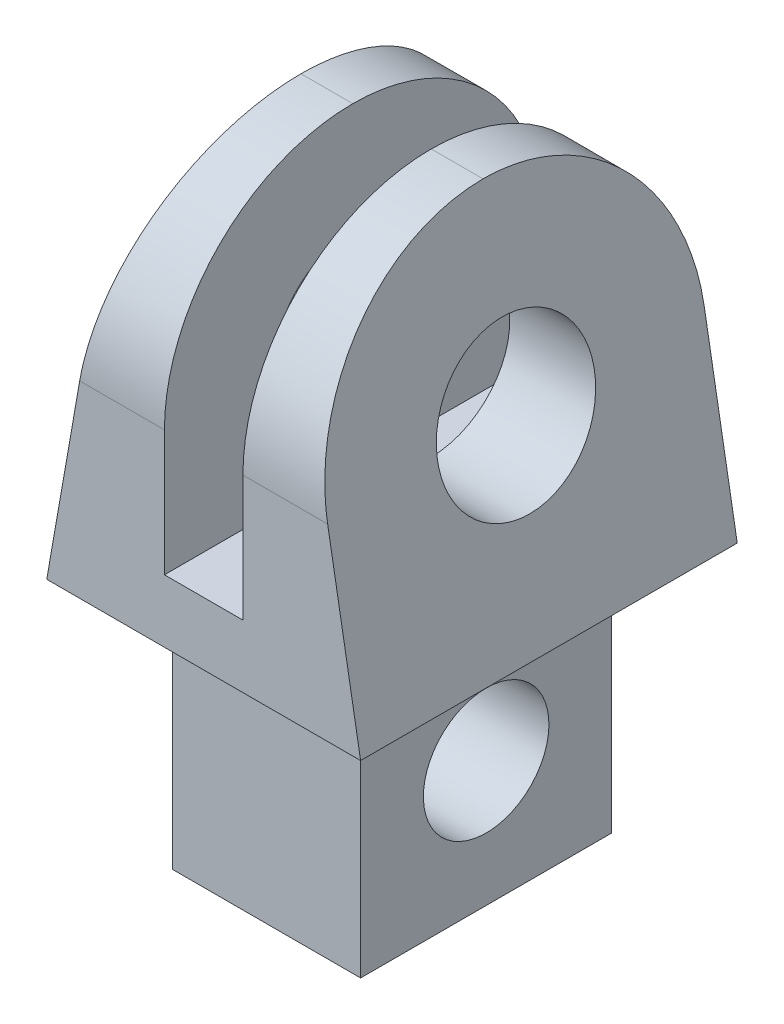
SolidWorks part; units mm, degrees
ref_plane "Front Plane" through (0, 0, 0) normal (1, 0, 0) x (0, 1, 0)
ref_plane "Top Plane" through (0, 0, 0) normal (0, 0, 1) x (0, 1, 0)
ref_plane "Right Plane" through (0, 0, 0) normal (0, 1, 0) x (-1, 0, 0)
sketch "Sketch1" plane through (0, 0, 0) normal (0, 0, 1) x (0, 1, 0)
  line L0 (0, 0) -> (0, 58378.1092) construction
  line L1 (0, 0) -> (58378.1092, 0) construction
  line L2 (0, 12.5) -> (0, -12.5)
  line L3 (0, 12.5) -> (100, 12.5)
  line L4 (100, 12.5) -> (100, 29)
  line L5 (100, 29) -> (-20, 50)
  line L6 (-20, 50) -> (-20, -50)
  line L7 (100, -12.5) -> (100, -29)
  line L8 (0, -12.5) -> (100, -12.5)
  line L9 (100, -29) -> (-20, -50)
  line L11 (-20, 30) -> (-100, 30)
  line L12 (-20, 30) -> (-20, -30)
  line L13 (-20, -30) -> (-100, -30)
  line L14 (-100, 30) -> (-100, -30)
  point P8 (0, 0)
  point P15 (0, 0)
  point P16 (-20, 0)
  dimension "D1" = 100
  dimension "D2" = 25
  dimension "D3" = 58
  dimension "D4" = 120
  dimension "D5" = 20
  dimension "D6" = 60
  dimension "D7" = 80
extrude "Boss-Extrude1" add sketch "Sketch1" along normal mid plane 80 contours L11 L14 L13 L6 region at (0, -60, 0)
extrude "Boss-Extrude2" add sketch "Sketch1<3>" along normal mid plane 120 contours L9 L7 L8 L2 L3 L4 L5 L6 region at (0, -1.562, 0)
sketch "Sketch1<3>" plane through (0, 0, 0) normal (0, 0, 1) x (0, 1, 0) same geometry as "Sketch1"
sketch "Sketch2" plane through (0, 0, 0) normal (1, 0, 0) x (0, 1, 0)
  line L0 (40, 60) -> (100, 60)
  line L1 (100, 60) -> (100, -60)
  line L2 (100, -60) -> (40, -60)
  line L4 (55, 0) -> (-55, 0) construction
  line L5 (-20, 60) -> (-20, -60) construction
  arc A0 (40, 60) -> (40, -60) centre (40, 0) cw
  circle A1 centre (40, 0) radius 25
  dimension "D2" = 60
  dimension "D3" = 50
  dimension "D1" = 60
extrude "Cut-Extrude2" cut sketch "Sketch2" against normal mid plane 120 contours A1
fillet "Fillet1" radius 60 4 edges at (-20.75, 100, -60) (20.75, 100, -60) (-20.75, 100, 60) (20.75, 100, 60)
sketch "Sketch3" plane through (30, 0, 0) normal (1, 0, 0) x (0, 1, 0)
  line L0 (-100, 40) -> (-100, -40) construction
  line L1 (-20, 40) -> (-100, 40) construction
  circle A0 centre (-60, 0) radius 20
  dimension "D1" = 40
  dimension "D2" = 40
  dimension "D3" = 40
extrude "Cut-Extrude3" cut sketch "Sketch3" against normal mid plane 120
